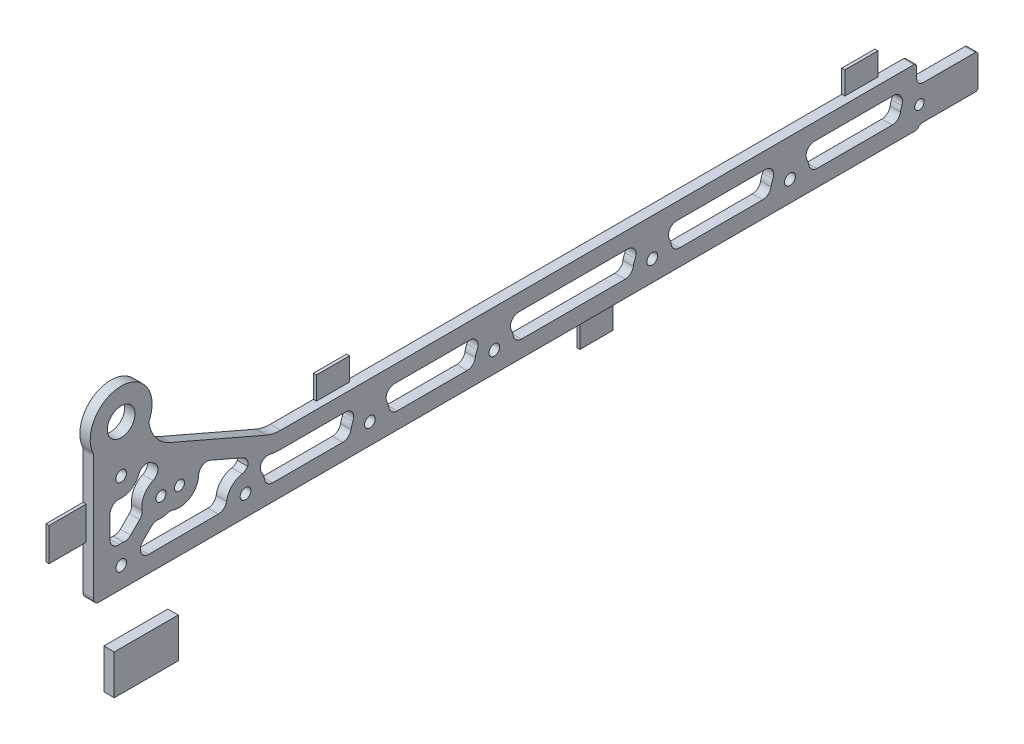
SolidWorks part; units mm, degrees
note: The reader was unsure of these and kept them because the rebuilt part matched: thickness of "Base-Flange1", "Sheet-Metal1", "Sheet-Metal4", "Sheet-Metal5", "Sheet-Metal6", "Sheet-Metal7", "Sheet-Metal9", "Sheet-Metal10", "Sheet-Metal13", "Sheet-Metal14", "Sheet-Metal27", "Sheet-Metal29", "Sheet-Metal31", "Sheet-Metal32", "Sheet-Metal33", "Sheet-Metal34", "Sheet-Metal35", "Sheet-Metal37".
material "6061-T6 (SS)"
ref_plane "Front Plane" through (0, 0, 0) normal (0, 0, 1) x (1, 0, 0)
ref_plane "Top Plane" through (0, 0, 0) normal (0, 1, 0) x (1, 0, 0)
ref_plane "Right Plane" through (0, 0, 0) normal (1, 0, 0) x (0, 0, -1)
sketch "Sketch1" plane through (0, 0, 0) normal (1, 0, 0) x (0, 0, -1)
  line L0 (0, 24.765) -> (57.15, 0)
  line L1 (-25.4, -26.67) -> (-25.4, 24.765)
  line L2 (-25.4, 24.765) -> (0, 24.765) construction
  line L4 (-25.4, -26.67) -> (168.275, -26.67)
  line L5 (0, 24.765) -> (0, -26.67) construction
  line L6 (0, 0) -> (57.15, 0) construction
  line L7 (0, 10.9239) -> (25.2089, 0) construction
  line L8 (57.15, 0) -> (168.275, 0)
  line L9 (168.275, 0) -> (168.275, -26.67)
  line L10 (0, -2.9172) -> (-6.7321, 0) construction
  line L11 (0, 24.765) -> (0, 33.5994)
  line L13 (-25.4, 33.5994) -> (-25.4, 24.765)
  circle A0 centre (-12.7, 40.005) radius 6.35
  arc A1 (-25.4, 33.5994) -> (0, 33.5994) centre (-12.7, 40.005) cw
  point P20 (-12.7, 24.765)
  dimension "D8" = 26.1888
  dimension "D9" = 66.675
  dimension "D10" = 1.524
  dimension "D1" = 26.67
  dimension "D2" = 57.15
  dimension "D3" = 15.24
  dimension "D4" = 25.4
  dimension "D5" = 12.7
  dimension "D6" = 193.675
  dimension "D7" = 25.4
base flange "Base-Flange1" sketch "Sketch1" thickness 4.7625 reverse thickness direction no parameters "D1"=0.7366
sketch "Sketch6" plane through (0, 0, 0) normal (1, 0, 0) x (0, 0, -1)
  line L0 (-12.7, 24.765) -> (-12.7, -17.145) construction
  line L1 (0, 24.765) -> (-25.4, 24.765) construction
  line L2 (114.3, -17.145) -> (-12.7, -17.145) construction
  line L3 (-12.7, -17.145) -> (9.1281, -17.145) construction
  line L4 (0, 10.9239) -> (25.2089, 0) construction
  line L5 (57.15, 0) -> (0, 24.765) construction
  line L6 (0, 24.765) -> (0, -26.67) construction
  line L7 (0, 0) -> (57.15, 0) construction
  line L8 (-25.4, 24.765) -> (0, 24.765) construction
  line L9 (168.275, -26.67) -> (168.275, 0) construction
  line L10 (-25.4, 33.5994) -> (-25.4, -26.67) construction
  line L11 (-25.4, -26.67) -> (168.275, -26.67) construction
  line L14 (0, 10.9239) -> (25.2089, 0) construction
  line L15 (8.2346, 7.3555) -> (16.9743, 3.5683) construction
  circle A0 centre (-12.7, 18.415) radius 1.6383
  circle A6 centre (8.2346, 7.3555) radius 1.6383
  circle A7 centre (-12.7, 8.89) radius 1.6383
  circle A8 centre (-12.7, -0.635) radius 1.6383
  circle A9 centre (-12.7, -10.16) radius 1.6383
  circle A12 centre (16.9743, 3.5683) radius 1.6383
  circle A15 centre (-12.7, -17.145) radius 1.6383
  circle A16 centre (9.1281, -17.145) radius 1.6383
  circle A17 centre (30.9562, -17.145) radius 1.6383
  circle A18 centre (52.7844, -17.145) radius 1.6383
  circle A19 centre (74.6125, -17.145) radius 1.6383
  circle A20 centre (96.4406, -17.145) radius 1.6383
  circle A21 centre (118.2687, -17.145) radius 1.6383
  circle A22 centre (140.0969, -17.145) radius 1.6383
  circle A23 centre (-12.7, -29.21) radius 1.6383 [skipped]
  circle A24 centre (-12.7, -19.685) radius 1.6383 [skipped]
  circle A25 centre (161.925, -17.145) radius 1.6383
  point P38 (12.6045, 5.4619)
  point P68 (161.925, -17.145)
  dimension "D2" = 3.2766
  dimension "D3" = 6.35
  dimension "D5" = 9.525
  dimension "D6" = 9
  dimension "D7" = 6.35
  dimension "D9" = 0.5655
  dimension "D1" = 9.525
  dimension "D8" = 9.525
  dimension "D4" = 6
sketch "Sketch13" plane through (0, 0, 0) normal (1, 0, 0) x (0, 0, -1)
  line L0 (-25.4, -26.67) -> (168.275, -26.67) construction
  line L2 (-25.4, 33.5994) -> (-25.4, -26.67) construction
  line L4 (5.5991, 1.2807) -> (14.1081, 1.2807) construction
  circle A0 centre (5.5991, 1.2807) radius 2.286
  circle A1 centre (14.1081, 1.2807) radius 2.286
  dimension "D1" = 4.572
  dimension "D2" = 13.081
  dimension "D3" = 27.9507
  dimension "D4" = 30.9991
extrude "Cut-Extrude1" cut sketch "Sketch13" against normal through all normal cut yes
hole_wizard "CSK for #10 Flat Head Machine Screw (100)2" [suppressed] positions "Sketch9" profile "Sketch10" countersink size "#10" standard "ANSI Inch"
sketch "Sketch9" plane through (-1.524, 0, 0) normal (-1, 0, 0) x (0, 0, 1)
  point P60 (12.7, 27.5433)
  point P63 (12.7, 18.0183)
  point P66 (12.7, 8.4933)
  point P69 (12.7, -1.0317)
  point P72 (12.7, -10.5567)
  point P75 (12.7, -20.0817)
  point P78 (-8.3159, 11.8745)
  point P81 (-15.9573, 6.1882)
  point P84 (-6.35, -12.7)
  point P87 (-15.4214, -12.7)
  point P90 (-24.4929, -12.7)
  point P93 (-33.5643, -12.7)
  point P96 (-42.6357, -12.7)
  point P99 (-51.7071, -12.7)
  point P102 (-60.7786, -12.7)
  point P105 (-69.85, -12.7)
sketch "Sketch10" plane through (-1.524, 27.5433, 12.7) normal (0, 1, 0) x (0, 0, 1)
  line L0 (0, 0) -> (0, 1.524)
  line L1 (0, 1.524) -> (1.6383, 1.524)
  line L2 (1.6383, 1.524) -> (1.6383, 1.3208)
  line L3 (1.6383, 1.3208) -> (2.9591, 0)
  line L5 (2.9591, 0) -> (0, 0)
  line L6 (-1.6383, 1.3208) -> (-2.9591, 0) construction
  line L11 (0, -6.35) -> (0, 107.95) construction
  dimension "Thru Hole Dia." = 3.2766
  dimension "Thru Hole Depth" = 1.524
  dimension "Near C'Sink Dia." = 5.9182
  dimension "Near C'Sink Angle" = 90
hole_wizard "CSK for #10 Flat Head Machine Screw (100)3" [suppressed] positions "Sketch11" profile "Sketch12" countersink size "#10" standard "ANSI Inch"
sketch "Sketch11" plane through (0, 0, 0) normal (1, 0, 0) x (0, 0, -1)
  point P108 (-12.7, 27.5433)
  point P111 (-12.7, 18.0183)
  point P114 (-12.7, 8.4933)
  point P117 (-12.7, -1.0317)
  point P120 (-12.7, -10.5567)
  point P123 (-12.7, -20.0817)
  point P126 (8.3159, 11.8745)
  point P129 (15.9573, 6.1882)
  point P132 (6.35, -12.7)
  point P135 (15.4214, -12.7)
  point P138 (24.4929, -12.7)
  point P141 (33.5643, -12.7)
  point P144 (42.6357, -12.7)
  point P147 (51.7071, -12.7)
  point P150 (60.7786, -12.7)
  point P153 (69.85, -12.7)
sketch "Sketch12" plane through (0, 27.5433, 12.7) normal (0, 1, 0) x (0, 0, -1)
  line L0 (0, 0) -> (0, 2.286)
  line L1 (0, 2.286) -> (1.6383, 2.286)
  line L2 (1.6383, 2.286) -> (1.6383, 1.3208)
  line L3 (1.6383, 1.3208) -> (2.9591, 0)
  line L5 (2.9591, 0) -> (0, 0)
  line L6 (-1.6383, 1.3208) -> (-2.9591, 0) construction
  line L11 (0, -6.35) -> (0, 107.95) construction
  dimension "Thru Hole Dia." = 3.2766
  dimension "Thru Hole Depth" = 2.286
  dimension "Near C'Sink Dia." = 5.9182
  dimension "Near C'Sink Angle" = 90
fillet "Fillet1" radius 16.51 2 edges at (-2.3813, 0, -57.15) (-2.3813, 24.765, 0)
hole_wizard "#10 (0.1935) Diameter Hole1" positions "Sketch14" profile "Sketch15" hole size "#10" standard "ANSI Inch" end condition through all
sketch "Sketch14" plane through (0, 0, 0) normal (1, 0, 0) x (0, 0, -1)
  line L1 (158.75, -17.145) -> (101.6, -17.145) construction
  line L2 (101.6, -17.145) -> (44.45, -17.145) construction
  line L3 (44.45, -17.145) -> (-12.7, -17.145) construction
  line L4 (-12.7, -17.145) -> (-12.7, 18.415) construction
  line L5 (-12.7, 18.415) -> (-12.7, 40.005) construction
  line L7 (-25.4, -26.67) -> (168.275, -26.67) construction
  point P41 (-12.7, -17.145)
  point P44 (44.45, -17.145)
  point P47 (101.6, -17.145)
  point P50 (158.75, -17.145)
  point P58 (-12.7, 18.415)
  dimension "D1" = 21.59
  dimension "D2" = 9.525
  dimension "D3" = 57.15
sketch "Sketch15" plane through (0, -17.145, 12.7) normal (0, 1, 0) x (0, 0, -1)
  line L0 (0, 0) -> (0, 4.7625)
  line L1 (0, 4.7625) -> (2.4574, 4.7625)
  line L2 (2.4574, 4.7625) -> (2.4574, 0)
  line L5 (2.4574, 0) -> (0, 0)
  line L11 (0, -6.35) -> (0, 107.95) construction
  dimension "Thru Hole Dia." = 4.9149
  dimension "Thru Hole Depth" = 4.7625
sketch "Sketch22" [suppressed] plane through (0, 0, 0) normal (1, 0, 0) x (0, 0, -1)
  line L1 (-75.7892, -29.5873) -> (-96.2835, -29.5873)
  line L2 (-75.7892, -29.5873) -> (-75.7892, -6.7214)
  line L3 (-75.7892, -6.7214) -> (-96.2835, -6.7214)
  line L4 (-96.2835, -29.5873) -> (-96.2835, -6.7214)
  dimension "D1" = 22.8659
  dimension "D2" = 20.4944
extrude "Boss-Extrude2" [suppressed] add sketch "Sketch22" against normal up to surface (4.7625 mm away) separate body
sketch "Sketch23" [suppressed] plane through (-4.7625, 0, 0) normal (-1, 0, 0) x (0, 0, 1)
  line L0 (25.4, 10.3433) -> (25.4, -4.8967)
  line L1 (25.4, 10.3433) -> (37.5677, 10.3433)
  line L2 (25.4, -4.8967) -> (37.5677, -4.8967)
  line L3 (37.5677, 10.3433) -> (37.5677, -4.8967)
  line L4 (25.4, 34.8694) -> (25.4, -25.4) construction
  line L5 (-91.8385, 0) -> (-76.5985, 0)
  line L6 (-91.8385, 0) -> (-91.8385, 9.2269)
  line L7 (-76.5985, 0) -> (-76.5985, 9.2269)
  line L8 (-91.8385, 9.2269) -> (-76.5985, 9.2269)
  line L9 (-114.3, 0) -> (-60.7335, 0) construction
  line L10 (-26.0856, -25.4) -> (-41.3256, -25.4)
  line L11 (-26.0856, -25.4) -> (-26.0856, -39.6506)
  line L12 (-41.3256, -25.4) -> (-41.3256, -39.6506)
  line L13 (-26.0856, -39.6506) -> (-41.3256, -39.6506)
  line L14 (25.4, -25.4) -> (-114.3, -25.4) construction
  dimension "D1" = 15.24
  dimension "D2" = 19.0897
  dimension "D3" = 14.2506
extrude "Boss-Extrude3" [suppressed] add sketch "Sketch23" against normal blind 1.27
fillet "Fillet4" radius 2.54 5 edges at (-2.3813, -26.67, -168.275) (-2.3813, 0, -168.275) (-2.3813, 33.5994, 0) (-2.3813, 33.5994, 25.4) (-2.3813, -26.67, 25.4)
hole_wizard "#10-32 Tapped Hole1" [suppressed] positions "Sketch18" profile "Sketch19" tap size "#10-32" standard "ANSI Inch"
sketch "Sketch18" plane through (0, 0, 0) normal (1, 0, 0) x (0, 0, -1)
  line L0 (137.16, 0) -> (60.7335, 0) construction
  line L1 (139.7, -22.86) -> (139.7, -2.54) construction
  point P1 (86.36, -6.35)
  dimension "D1" = 6.35
  dimension "D2" = 53.34
sketch "Sketch19" plane through (0, -6.35, -86.36) normal (0, 1, 0) x (0, 0, -1)
  line L0 (0, 0) -> (0, 13.2529)
  line L1 (0, 13.2529) -> (2.0193, 12.0396)
  line L2 (2.0193, 12.0396) -> (2.0193, 0)
  line L5 (2.0193, 0) -> (0, 0)
  line L10 (0, 13.2529) -> (-2.0193, 12.0396) construction
  line L11 (0, -6.35) -> (0, 107.95) construction
  dimension "Tap Drill Dia." = 4.0386
  dimension "Tap Drill Depth" = 12.0396
  dimension "Drill Angle" = 118
cosmetic thread "Hole Thread1" [suppressed]
pattern_linear "LPattern1" [suppressed] count 3 spacing 19.05
sketch "Sketch24" plane through (0, 0, 0) normal (1, 0, 0) x (0, 0, -1)
  line L0 (-12.7, -17.145) -> (5.5991, 1.2807) construction
  line L1 (-9.9967, -19.8298) -> (8.3024, -1.4041)
  line L2 (-15.4033, -14.4602) -> (2.8957, 3.9655)
  line L10 (-17.78, 33.0212) -> (-17.78, -19.05)
  line L11 (-17.78, -19.05) -> (160.655, -19.05)
  line L12 (160.655, -19.05) -> (160.655, -7.62)
  line L13 (160.655, -7.62) -> (60.5734, -7.62)
  line L14 (50.9791, -5.6306) -> (6.7866, 13.5195)
  line L15 (-17.78, 33.0212) -> (-17.78, -19.05)
  line L16 (-17.78, -19.05) -> (160.655, -19.05)
  line L17 (160.655, -19.05) -> (160.655, -7.62)
  line L18 (160.655, -7.62) -> (60.5734, -7.62)
  line L19 (50.9791, -5.6306) -> (6.7866, 13.5195)
  circle A0 centre (-12.7, 18.415) radius 8.8074
  circle A1 centre (-12.7, -17.145) radius 8.8074
  circle A2 centre (44.45, -17.145) radius 8.8074
  circle A3 centre (101.6, -17.145) radius 8.8074
  circle A4 centre (158.75, -17.145) radius 8.8074
  circle A5 centre (5.5991, 1.2807) radius 8.8074
  circle A6 centre (14.1081, 1.2807) radius 8.8074
  arc A7 (52.1248, -12.8244) -> (56.1442, -7.21) centre (55.4449, -10.9553) cw
  arc A8 (41.6198, -8.8047) -> (41.9104, -1.7008) centre (40.3955, -5.1967) ccw
  arc A9 (-4.5133, 15.167) -> (1.3944, 16.7481) centre (-0.9718, 13.762) cw
  arc A10 (1.9484, 9.2959) -> (2.5526, 15.8855) centre (0.3691, 12.7632) ccw
  arc A11 (-2.7721, -12.5552) -> (-0.0687, -19.05) centre (-0.0687, -15.24) ccw
  circle A15 centre (-12.7, 18.415) radius 2.4574 construction
  arc A23 (-7.3762, 31.4345) -> (6.7866, 13.5195) centre (16.3809, 35.6601) ccw
  arc A24 (-6.6622, 37.3296) -> (-18.7036, 37.2538) centre (-12.7, 40.005) ccw
  arc A25 (-6.6622, 37.3296) -> (-7.3762, 31.4345) centre (2.6268, 33.2137) ccw
  arc A26 (-6.6622, 37.3296) -> (-7.3762, 31.4345) centre (2.6268, 33.2137) ccw
  arc A27 (-17.78, 33.0212) -> (-18.7036, 37.2538) centre (-27.94, 33.0212) ccw
  arc A28 (50.9791, -5.6306) -> (60.5734, -7.62) centre (60.5734, 16.51) ccw
  arc A29 (-7.7491, 35.6345) -> (6.7866, 13.5195) centre (16.3809, 35.6601) ccw
  arc A30 (-7.7491, 35.6345) -> (-18.7036, 37.2538) centre (-12.7, 40.005) ccw
  arc A34 (50.9791, -5.6306) -> (60.5734, -7.62) centre (60.5734, 16.51) ccw
  arc A35 (-17.78, 33.0212) -> (-18.7036, 37.2538) centre (-27.94, 33.0212) ccw
  dimension "D2" = 6.35
  dimension "D3" = 3.81
  dimension "D1" = 7.62
  dimension "D4" = 3.81
  dimension "D5" = 3.81
extrude "Cut-Extrude2" [suppressed] cut sketch "Sketch24" against normal through all contours A29 A9 A0 L15 A1 L2 A5 A10 | A2 A8 L19 A6 A5 L1 A1 L16 | A34 A7 A2 L16 A3 L18 | A4 L18 A3 L16
fillet "Fillet5" [suppressed] radius 3.81
sketch "Sketch25" [suppressed] plane through (-4.7625, 0, 0) normal (-1, 0, 0) x (0, 0, 1)
  line L0 (22.86, -25.4) -> (-165.735, -25.4) construction
  line L1 (25.4, 34.2912) -> (25.4, -22.86) construction
  line L4 (-89.7914, -7.62) -> (-60.7335, -7.62) construction
  circle A0 centre (-63.5, -17.145) radius 4.7625
  dimension "D1" = 9.525
  dimension "D4" = 4.7625
  dimension "D2" = 8.255
  dimension "D3" = 88.9
extrude "Boss-Extrude4" [suppressed] add sketch "Sketch25" against normal up to surface (4.7625 mm away)
sketch "Sketch26" [suppressed] plane through (-4.7625, 0, 0) normal (-1, 0, 0) x (0, 0, 1)
  circle A0 centre (-63.5, -17.145) radius 2.3813
  dimension "D1" = 4.7625
fillet "Fillet6" [suppressed] radius 6.35
hole_wizard " Tapped Hole2" [suppressed] positions "Sketch29" profile "Sketch30" tap size "#8-32" standard "ANSI Inch"
sketch "Sketch29" [suppressed] plane through (-4.7625, 0, 0) normal (-1, 0, 0) x (0, 0, 1)
  point P0 (-63.5, -17.145)
sketch "Sketch30" plane through (-4.7625, -17.145, -63.5) normal (0, 1, 0) x (0, 0, 1)
  line L0 (0, 0) -> (0, 4.7625)
  line L1 (0, 4.7625) -> (2.0193, 4.7625)
  line L2 (2.0193, 4.7625) -> (2.0193, 0)
  line L5 (2.0193, 0) -> (0, 0)
  line L11 (0, -6.35) -> (0, 107.95) construction
  dimension "Thru Tap Drill Dia." = 3.4544
  dimension "Thru Tap Drill Depth" = 4.7625
cosmetic thread "Hole Thread2" [suppressed]
fillet "Fillet7" [suppressed] radius 3.048
sketch "Sketch32" [suppressed] plane through (-4.7625, 0, 0) normal (-1, 0, 0) x (0, 0, 1)
  line L0 (-184.253, -26.3369) -> (-208.5192, -26.3369)
  line L1 (-184.253, -26.3369) -> (-184.253, -4.36)
  line L2 (-208.5192, -26.3369) -> (-208.5192, -4.36)
  line L3 (-184.253, -4.36) -> (-208.5192, -4.36)
  dimension "D1" = 41.2067
  dimension "D2" = 32.5075
extrude "Boss-Extrude5" [suppressed] add sketch "Sketch32" against normal up to surface (4.7625 mm away) separate body
sketch "Sketch33" [suppressed] plane through (0, 0, 0) normal (1, 0, 0) x (0, 0, -1)
  line L0 (-25.4, 34.2912) -> (-25.4, -22.86) construction
  line L2 (-25.4, -10.134) -> (-25.4, 5.106)
  line L3 (-25.4, -10.134) -> (-34.1173, -10.134)
  line L4 (-25.4, 5.106) -> (-34.1173, 5.106)
  line L5 (-34.1173, -10.134) -> (-34.1173, 5.106)
  line L6 (168.275, -6.1621) -> (168.275, -21.4021)
  line L7 (168.275, -6.1621) -> (174.9331, -6.1621)
  line L8 (168.275, -21.4021) -> (174.9331, -21.4021)
  line L9 (174.9331, -6.1621) -> (174.9331, -21.4021)
  line L10 (168.275, -22.86) -> (168.275, -2.54) construction
  line L11 (62.6695, -25.4) -> (77.9095, -25.4)
  line L12 (62.6695, -25.4) -> (62.6695, -34.9885)
  line L13 (77.9095, -25.4) -> (77.9095, -34.9885)
  line L14 (62.6695, -34.9885) -> (77.9095, -34.9885)
  line L15 (-22.86, -25.4) -> (165.735, -25.4) construction
  line L16 (122.9051, 0) -> (138.1451, 0)
  line L17 (122.9051, 0) -> (122.9051, 11.3683)
  line L18 (138.1451, 0) -> (138.1451, 11.3683)
  line L19 (122.9051, 11.3683) -> (138.1451, 11.3683)
  line L20 (165.735, 0) -> (60.7335, 0) construction
  line L21 (20.9085, 16.51) -> (34.7772, 10.192)
  line L22 (20.9085, 16.51) -> (24.2006, 23.7364)
  line L23 (34.7772, 10.192) -> (38.0693, 17.4184)
  line L24 (24.2006, 23.7364) -> (38.0693, 17.4184)
  line L25 (53.889, 1.4856) -> (9.5634, 21.6783) construction
  dimension "D1" = 15.24
  dimension "D2" = 7.9409
extrude "Boss-Extrude6" [suppressed] add sketch "Sketch33" against normal blind 1.27
sketch "Sketch35" [suppressed] plane through (0, 0, 0) normal (1, 0, 0) x (0, 0, -1)
  line L0 (-25.4, -3.4789) -> (-25.4, 11.7611)
  line L1 (-25.4, -3.4789) -> (-43.416, -3.4789)
  line L2 (-25.4, 11.7611) -> (-43.416, 11.7611)
  line L3 (-43.416, -3.4789) -> (-43.416, 11.7611)
  line L4 (-25.4, 34.2912) -> (-25.4, -22.86) construction
  line L5 (15.126, 19.1443) -> (28.9947, 12.8263)
  line L6 (15.126, 19.1443) -> (19.3832, 28.4895)
  line L7 (28.9947, 12.8263) -> (33.2519, 22.1715)
  line L8 (19.3832, 28.4895) -> (33.2519, 22.1715)
  line L9 (53.889, 1.4856) -> (9.5634, 21.6783) construction
  line L10 (83.6261, -25.4) -> (98.8661, -25.4)
  line L11 (83.6261, -25.4) -> (83.6261, -34.1917)
  line L12 (98.8661, -25.4) -> (98.8661, -34.1917)
  line L13 (83.6261, -34.1917) -> (98.8661, -34.1917)
  line L14 (-22.86, -25.4) -> (165.735, -25.4) construction
  line L15 (126.1294, 0) -> (141.3694, 0)
  line L16 (126.1294, 0) -> (126.1294, 8.0687)
  line L17 (141.3694, 0) -> (141.3694, 8.0687)
  line L18 (126.1294, 8.0687) -> (141.3694, 8.0687)
  line L19 (165.735, 0) -> (60.7335, 0) construction
  line L20 (168.275, -21.2983) -> (168.275, -6.0583)
  line L21 (168.275, -21.2983) -> (173.5241, -21.2983)
  line L22 (168.275, -6.0583) -> (173.5241, -6.0583)
  line L23 (173.5241, -21.2983) -> (173.5241, -6.0583)
  line L24 (168.275, -22.86) -> (168.275, -2.54) construction
  dimension "D1" = 15.24
  dimension "D2" = 5.2491
extrude "Boss-Extrude7" [suppressed] add sketch "Sketch35" against normal blind 1.27
sketch "Sketch37" plane through (-4.7625, 0, 0) normal (-1, 0, 0) x (0, 0, 1)
  line L0 (-165.735, -26.67) -> (-353.0505, -26.67)
  line L2 (-355.6, -25.019) -> (-381, -25.019)
  line L3 (-381, -25.019) -> (-381, -9.271)
  line L4 (-381, -9.271) -> (-355.6, -9.271)
  line L5 (-352.806, -6.477) -> (-352.806, 0)
  line L6 (-352.806, 0) -> (-165.735, 0)
  line L7 (-168.275, -24.13) -> (-168.275, -2.54) construction
  line L8 (-168.275, -24.13) -> (-168.275, -2.54)
  line L9 (-381, -17.145) -> (-323.8598, -17.145) construction
  line L11 (-355.6, -25.019) -> (-355.6, -4.0005) construction
  line L12 (25.4, 33.0212) -> (25.4, -24.13) construction
  arc A0 (-165.735, 0) -> (-168.275, -2.54) centre (-165.735, -2.54) ccw construction
  arc A1 (-168.275, -24.13) -> (-165.735, -26.67) centre (-165.735, -24.13) ccw construction
  arc A2 (-165.735, 0) -> (-168.275, -2.54) centre (-165.735, -2.54) ccw
  arc A3 (-168.275, -24.13) -> (-165.735, -26.67) centre (-165.735, -24.13) ccw
  arc A4 (-353.0505, -26.67) -> (-355.6, -25.019) centre (-355.6, -27.813) ccw
  arc A5 (-355.6, -9.271) -> (-352.806, -6.477) centre (-355.6, -6.477) ccw
  circle A6 centre (-231.3432, -17.145) radius 2.4892
  circle A7 centre (-294.5892, -17.145) radius 2.4892
  circle A9 centre (-354.076, -17.145) radius 2.159
  dimension "D4" = 2.794
  dimension "D5" = 25.4
  dimension "D6" = 254.254
  dimension "D7" = 317.5
  dimension "D8" = 4.9784
  dimension "D9" = 4.318
  dimension "D1" = 1.651
  dimension "D2" = 9.525
  dimension "D3" = 381
  dimension "D10" = 379.476
extrude "Boss-Extrude8" add sketch "Sketch37" against normal through all
sketch "Sketch39" [suppressed] plane through (-4.7625, 0, 0) normal (-1, 0, 0) x (0, 0, 1)
  line L0 (-146.9414, -7.62) -> (-351.0058, -7.62)
  line L1 (-146.2772, -17.78) -> (-345.477, -17.78)
  circle A0 centre (-354.076, -15.875) radius 8.8075
  circle A1 centre (-294.5892, -15.875) radius 8.8075
  circle A2 centre (-231.3432, -15.875) radius 8.8074
  circle A3 centre (-158.75, -15.875) radius 8.8074
  arc A4 (-150.0435, -14.5452) -> (-150.5072, -12.7722) centre (-158.75, -15.875) ccw construction
  dimension "D1" = 1.386
extrude "Cut-Extrude3" [suppressed] cut sketch "Sketch39" against normal through all contours A1 L0 A0 L1 | A2 L0 A1 L1 | A3 L0 A2 L1
fillet "Fillet8" [suppressed] radius 3.81
sketch "Sketch46" plane through (0, 0, 0) normal (1, 0, 0) x (0, 0, -1)
  line L0 (-12.7, -17.145) -> (5.5991, 1.2807) construction
  line L1 (-9.9967, -19.8298) -> (8.3024, -1.4041)
  line L2 (-15.4033, -14.4602) -> (2.8957, 3.9655)
  line L3 (44.45, -17.145) -> (51.3619, -1.1944) construction
  line L4 (101.6, -17.145) -> (101.6, 0) construction
  line L5 (352.806, 0) -> (60.5734, 0) construction
  line L6 (158.75, -17.145) -> (158.75, 0) construction
  line L7 (231.3432, -17.145) -> (231.3432, 3.1296) construction
  line L8 (294.5892, -17.145) -> (294.5892, 6.8724) construction
  line L9 (297.7642, -17.145) -> (297.7642, 6.8724)
  line L10 (234.5182, -17.145) -> (234.5182, 3.1296)
  line L11 (161.925, -17.145) -> (161.925, 0)
  line L12 (104.775, -17.145) -> (104.775, 0)
  line L13 (46.4846, -20.4351) -> (54.4474, -2.0594)
  line L14 (291.4142, -17.145) -> (291.4142, 6.8724)
  line L15 (228.1682, -17.145) -> (228.1682, 3.1296)
  line L16 (-17.78, -19.05) -> (349.9732, -19.05)
  line L17 (355.6, -17.399) -> (373.38, -17.399)
  line L18 (373.38, -17.399) -> (373.38, -16.891)
  line L19 (373.38, -16.891) -> (355.6, -16.891)
  line L21 (345.2489, -7.62) -> (60.5734, -7.62)
  line L22 (50.9791, -5.6306) -> (6.7866, 13.5195)
  line L23 (-17.78, 33.0212) -> (-17.78, -19.05)
  line L24 (-17.78, -19.05) -> (349.9732, -19.05)
  line L25 (355.6, -17.399) -> (373.38, -17.399)
  line L26 (373.38, -17.399) -> (373.38, -16.891)
  line L27 (373.38, -16.891) -> (355.6, -16.891)
  line L29 (345.2489, -7.62) -> (60.5734, -7.62)
  line L30 (50.9791, -5.6306) -> (6.7866, 13.5195)
  line L31 (-17.78, 33.0212) -> (-17.78, -19.05)
  line L32 (155.575, -17.145) -> (155.575, 0)
  line L33 (98.425, -17.145) -> (98.425, 0)
  line L34 (40.5621, -18.1318) -> (49.326, 2.0925)
  line L35 (44.45, -17.145) -> (50.5452, -3.0793) construction
  line L36 (47.3632, -18.4074) -> (53.4584, -4.3417) construction
  line L37 (41.5368, -15.8826) -> (47.6319, -1.8169) construction
  arc A0 (1.9484, 9.2959) -> (2.5526, 15.8855) centre (0.3691, 12.7632) ccw
  arc A1 (22.9072, 0.8978) -> (28.2285, 4.228) centre (26.7136, 0.7321) cw
  arc A2 (93.7478, -13.1557) -> (90.3511, -7.62) centre (90.3511, -11.43) ccw
  arc A3 (-2.7721, -12.5552) -> (-0.0687, -19.05) centre (-0.0687, -15.24) ccw
  arc A4 (109.4522, -13.1557) -> (112.8489, -7.62) centre (112.8489, -11.43) cw
  arc A5 (150.8978, -13.1557) -> (147.5011, -7.62) centre (147.5011, -11.43) ccw
  arc A6 (166.6022, -13.1557) -> (169.9989, -7.62) centre (169.9989, -11.43) cw
  arc A7 (223.491, -13.1557) -> (220.0943, -7.62) centre (220.0943, -11.43) ccw
  circle A8 centre (-12.7, 18.415) radius 8.8074
  circle A9 centre (5.5991, 1.2807) radius 8.8074
  circle A10 centre (14.1081, 1.2807) radius 8.8074
  circle A11 centre (-12.7, -17.145) radius 8.8074
  circle A12 centre (44.45, -17.145) radius 8.8074
  circle A13 centre (101.6, -17.145) radius 8.8074
  arc A14 (239.1954, -13.1557) -> (242.5921, -7.62) centre (242.5921, -11.43) cw
  circle A15 centre (158.75, -17.145) radius 8.8074
  arc A16 (355.6, -17.399) -> (349.9732, -19.05) centre (355.6, -27.813) ccw
  arc A17 (345.2489, -7.62) -> (355.6, -16.891) centre (355.6, -6.477) ccw
  arc A18 (50.9791, -5.6306) -> (60.5734, -7.62) centre (60.5734, 16.51) ccw
  arc A19 (-7.3762, 31.4345) -> (6.7866, 13.5195) centre (16.3809, 35.6601) ccw
  arc A20 (-6.6622, 37.3296) -> (-7.3762, 31.4345) centre (2.6268, 33.2137) ccw
  arc A21 (-6.6622, 37.3296) -> (-18.7036, 37.2538) centre (-12.7, 40.005) ccw
  arc A22 (-17.78, 33.0212) -> (-18.7036, 37.2538) centre (-27.94, 33.0212) ccw
  arc A23 (355.6, -17.399) -> (349.9732, -19.05) centre (355.6, -27.813) ccw
  arc A24 (345.2489, -7.62) -> (355.6, -16.891) centre (355.6, -6.477) ccw
  arc A25 (50.9791, -5.6306) -> (60.5734, -7.62) centre (60.5734, 16.51) ccw
  arc A26 (-7.3762, 31.4345) -> (6.7866, 13.5195) centre (16.3809, 35.6601) ccw
  arc A27 (-6.6622, 37.3296) -> (-7.3762, 31.4345) centre (2.6268, 33.2137) ccw
  arc A28 (-6.6622, 37.3296) -> (-18.7036, 37.2538) centre (-12.7, 40.005) ccw
  arc A29 (-17.78, 33.0212) -> (-18.7036, 37.2538) centre (-27.94, 33.0212) ccw
  circle A30 centre (231.3432, -17.145) radius 8.8074
  circle A31 centre (294.5892, -17.145) radius 8.8075
  circle A32 centre (354.076, -17.145) radius 8.8075
  circle A33 centre (-12.7, -17.145) radius 2.4574 construction
  arc A34 (-4.5133, 15.167) -> (1.3944, 16.7481) centre (-0.9718, 13.762) cw
  arc A35 (286.737, -13.1557) -> (283.3403, -7.62) centre (283.3403, -11.43) ccw
  arc A36 (302.4414, -13.1557) -> (305.8381, -7.62) centre (305.8381, -11.43) cw
  dimension "D2" = 6.35
  dimension "D3" = 3.81
  dimension "D4" = 3.81
  dimension "D6" = 3.175
  dimension "D8" = 2.8676
  dimension "D1" = 7.62
  dimension "D5" = 3.81
  dimension "D7" = 3.175
extrude "Cut-Extrude4" cut sketch "Sketch46" against normal through all
fillet "Fillet10" radius 3.81 23 edges at (-2.3813, -12.1165, -346.8451) (-2.3813, -19.05, -345.477) (-2.3813, -19.05, -303.1882) (-2.3813, -19.05, -285.9902) (-2.3813, -19.05, -239.9422) (-2.3813, -19.05, -222.7442) (-2.3813, -19.05, -167.349) (-2.3813, -19.05, -150.151) (-2.3813, -19.05, -110.199) (-2.3813, -19.05, -93.001) (-2.3813, -19.05, -53.049) (-2.3813, -19.05, -35.851) (-2.3813, -10.8694, -50.6297) (-2.3813, -6.2722, -52.6218) (-2.3813, -7.0383, -2.7069) (-2.3813, -6.431, -9.8536) (-2.3813, -3.8065, -46.7697) (-2.3813, -8.3446, -44.8032) (-2.3813, -1.6688, 2.6998) (-2.3813, -9.9502, 17.78) (-2.3813, 11.2202, 17.78) (-2.3813, -8.826, 9.8078) (-2.3813, -7.62, -345.2489)
fillet "Fillet9" radius 1.27 4 edges at (-2.3812, -26.67, -353.0505) (-2.3812, -25.019, -381) (-2.3812, -9.271, -381) (-2.3812, 0, -352.806)
sketch "Sketch41" plane through (-4.7625, 0, 0) normal (-1, 0, 0) x (0, 0, 1)
  line L0 (-351.536, 0) -> (-60.5734, 0) construction
  line L1 (-338.3853, 0) -> (-323.1453, 0)
  line L2 (-338.3853, 0) -> (-338.3853, 10.4268)
  line L3 (-338.3853, 10.4268) -> (-323.1453, 10.4268)
  line L4 (-323.1453, 0) -> (-323.1453, 10.4268)
  line L5 (22.86, -26.67) -> (-352.3299, -26.67) construction
  line L6 (-216.7038, -26.67) -> (-201.4638, -26.67)
  line L7 (-216.7038, -26.67) -> (-216.7038, -39.9756)
  line L8 (-216.7038, -39.9756) -> (-201.4638, -39.9756)
  line L9 (-201.4638, -26.67) -> (-201.4638, -39.9756)
  line L10 (25.4, 33.0212) -> (25.4, -24.13) construction
  line L11 (-95.6188, 0) -> (-80.3788, 0)
  line L12 (-95.6188, 0) -> (-95.6188, 10.4268)
  line L13 (-95.6188, 10.4268) -> (-80.3788, 10.4268)
  line L14 (-80.3788, 0) -> (-80.3788, 10.4268)
  line L15 (25.4, 11.9478) -> (42.4659, 11.9478)
  line L16 (25.4, 11.9478) -> (25.4, -3.2922)
  line L17 (25.4, -3.2922) -> (42.4659, -3.2922)
  line L18 (42.4659, 11.9478) -> (42.4659, -3.2922)
  dimension "D1" = 15.24
  dimension "D2" = 17.0659
extrude "Boss-Extrude9" add sketch "Sketch41" against normal blind 1.397
sketch "Sketch43" plane through (0, 0, 0) normal (1, 0, 0) x (0, 0, -1)
  line L1 (-15.8749, -49.9791) -> (13.5373, -49.9791)
  line L2 (-15.8749, -49.9791) -> (-15.8749, -68.2456)
  line L3 (-15.8749, -68.2456) -> (13.5373, -68.2456)
  line L4 (13.5373, -49.9791) -> (13.5373, -68.2456)
  dimension "D1" = 18.2665
  dimension "D2" = 29.4122
extrude "Boss-Extrude10" add sketch "Sketch43" against normal through all separate body
sketch "Bend-Lines1" [suppressed] plane through (0, 0, 0) normal (0, 1, 0) x (1, 0, 0)
sketch "Bounding-Box1" [suppressed] plane through (0, 0, 0) normal (0, 1, 0) x (1, 0, 0)
sheet metal parameters "Sheet-Metal1" thickness 4.7625 parameters "D1"=0.7366
flat pattern "Flat-Pattern1" [suppressed]
sketch "Bend-Lines2" plane through (0, 0, 0) normal (0, 1, 0) x (1, 0, 0)
sketch3d "Bounding-Box2" [suppressed]
  line L0 (76.2, -25.4, 0) -> (-25.4, -25.4, 0) construction
  line L1 (76.2, 33.8933, 0) -> (-25.4, 33.8933, 0) construction
  line L2 (76.2, -25.4, 0) -> (76.2, 33.8933, 0) construction
  line L3 (-25.4, -25.4, 0) -> (-25.4, 33.8933, 0) construction
sheet metal parameters "Sheet-Metal4" [suppressed] thickness 4.7625 parameters "D1"=0.7366, "D7"=1.524
flat pattern "Flat-Pattern1"
sketch "Bend-Lines2" plane through (0, 0, 0) normal (0, 1, 0) x (1, 0, 0)
sketch3d "Bounding-Box2" [suppressed]
  line L0 (76.2, -25.4, 0) -> (-25.4, -25.4, 0) construction
  line L1 (76.2, 33.8933, 0) -> (-25.4, 33.8933, 0) construction
  line L2 (76.2, -25.4, 0) -> (76.2, 33.8933, 0) construction
  line L3 (-25.4, -25.4, 0) -> (-25.4, 33.8933, 0) construction
sheet metal parameters "Sheet-Metal5" [suppressed] thickness 4.7625 parameters "D1"=0.7366, "D7"=1.524
flat pattern "Flat-Pattern1"
sketch "Bend-Lines2" plane through (0, 0, 0) normal (0, 1, 0) x (1, 0, 0)
sketch3d "Bounding-Box2" [suppressed]
  line L0 (76.2, -25.4, 0) -> (-25.4, -25.4, 0) construction
  line L1 (76.2, 33.8933, 0) -> (-25.4, 33.8933, 0) construction
  line L2 (76.2, -25.4, 0) -> (76.2, 33.8933, 0) construction
  line L3 (-25.4, -25.4, 0) -> (-25.4, 33.8933, 0) construction
sheet metal parameters "Sheet-Metal6" thickness 4.7625 parameters "D1"=0.7366, "D7"=2.286
flat pattern "Flat-Pattern1"
sketch "Bend-Lines2" plane through (0, 0, 0) normal (0, 1, 0) x (1, 0, 0)
sketch3d "Bounding-Box2" [suppressed]
  line L0 (88.8958, 12.7065, 0) -> (-12.7009, 12.699, 0) construction
  line L1 (88.9019, -69.9128, 0) -> (-12.6948, -69.9203, 0) construction
  line L2 (88.8958, 12.7065, 0) -> (88.9019, -69.9128, 0) construction
  line L3 (-12.7009, 12.699, 0) -> (-12.6948, -69.9203, 0) construction
sheet metal parameters "Sheet-Metal7" thickness 4.7625 parameters "D1"=0.7366, "D7"=2.286
flat pattern "Flat-Pattern1"
sketch "Bend-Lines2" plane through (0, 0, 0) normal (0, 1, 0) x (1, 0, 0)
sketch3d "Bounding-Box2" [suppressed]
  line L0 (180.975, 14.224, 0) -> (-14.224, 14.224, 0) construction
  line L1 (180.975, -66.675, 0) -> (-14.224, -66.675, 0) construction
  line L2 (180.975, 14.224, 0) -> (180.975, -66.675, 0) construction
  line L3 (-14.224, 14.224, 0) -> (-14.224, -66.675, 0) construction
sheet metal parameters "Sheet-Metal9" thickness 4.7625 parameters "D1"=0.7366, "D7"=2.286
flat pattern "Flat-Pattern1"
sketch "Bend-Lines2" plane through (0, 0, 0) normal (0, 1, 0) x (1, 0, 0)
sketch3d "Bounding-Box2" [suppressed]
  line L0 (133.35, 14.224, 0) -> (-14.224, 14.224, 0) construction
  line L1 (133.35, -66.675, 0) -> (-14.224, -66.675, 0) construction
  line L2 (133.35, 14.224, 0) -> (133.35, -66.675, 0) construction
  line L3 (-14.224, 14.224, 0) -> (-14.224, -66.675, 0) construction
sheet metal parameters "Sheet-Metal10" thickness 4.7625 parameters "D1"=0.7366, "D7"=2.286
flat pattern "Flat-Pattern1"
sketch "Bend-Lines2" plane through (0, 0, 0) normal (0, 1, 0) x (1, 0, 0)
sketch3d "Bounding-Box2" [suppressed]
  line L0 (152.4, 14.224, 0) -> (-14.224, 14.224, 0) construction
  line L1 (152.4, -66.675, 0) -> (-14.224, -66.675, 0) construction
  line L2 (152.4, 14.224, 0) -> (152.4, -66.675, 0) construction
  line L3 (-14.224, 14.224, 0) -> (-14.224, -66.675, 0) construction
sheet metal parameters "Sheet-Metal13" thickness 4.7625 parameters "D1"=0.7366, "D7"=2.286
flat pattern "Flat-Pattern1"
sketch "Bend-Lines2" plane through (0, 0, 0) normal (0, 1, 0) x (1, 0, 0)
sketch3d "Bounding-Box2" [suppressed]
  line L0 (127, 14.224, 0) -> (-14.224, 14.224, 0) construction
  line L1 (127, -66.675, 0) -> (-14.224, -66.675, 0) construction
  line L2 (127, 14.224, 0) -> (127, -66.675, 0) construction
  line L3 (-14.224, 14.224, 0) -> (-14.224, -66.675, 0) construction
sheet metal parameters "Sheet-Metal14" thickness 4.7625 parameters "D1"=0.7366, "D7"=2.286
flat pattern "Flat-Pattern1" [suppressed]
sketch "Bend-Lines2" plane through (0, 0, 0) normal (0, 1, 0) x (1, 0, 0)
sketch3d "Bounding-Box2" [suppressed]
  line L0 (180.975, 14.224, 0) -> (-14.224, 14.224, 0) construction
  line L1 (180.975, -66.675, 0) -> (-14.224, -66.675, 0) construction
  line L2 (180.975, 14.224, 0) -> (180.975, -66.675, 0) construction
  line L3 (-14.224, 14.224, 0) -> (-14.224, -66.675, 0) construction
sketch "Sketch26-6" [suppressed] plane through (-4.7625, 0, 0) normal (-1, 0, 0) x (0, 0, 1)
  circle A0 centre (-63.5, -17.145) radius 2.3813
  dimension "D1" = 4.7625
sketch "Sketch26-12" [suppressed] plane through (-4.7625, 0, 0) normal (-1, 0, 0) x (0, 0, 1)
  circle A0 centre (-63.5, -17.145) radius 2.3813
  dimension "D1" = 4.7625
sketch "Sketch26-13" [suppressed] plane through (-4.7625, 0, 0) normal (-1, 0, 0) x (0, 0, 1)
  circle A0 centre (-63.5, -17.145) radius 2.3813
  dimension "D1" = 4.7625
sketch "Sketch26-22" [suppressed] plane through (-4.7625, 0, 0) normal (-1, 0, 0) x (0, 0, 1)
  circle A0 centre (-63.5, -17.145) radius 2.3813
  dimension "D1" = 4.7625
sheet metal parameters "Sheet-Metal27" [suppressed] thickness 4.7625 parameters "D1"=0.7366, "D7"=2.286
flat pattern "Flat-Pattern1" [suppressed]
sketch "Bend-Lines2" plane through (0, 0, 0) normal (0, 1, 0) x (1, 0, 0)
sketch3d "Bounding-Box2" [suppressed]
  line L0 (180.975, 14.224, 0) -> (-14.224, 14.224, 0) construction
  line L1 (180.975, -66.675, 0) -> (-14.224, -66.675, 0) construction
  line L2 (180.975, 14.224, 0) -> (180.975, -66.675, 0) construction
  line L3 (-14.224, 14.224, 0) -> (-14.224, -66.675, 0) construction
sketch "Sketch26-1" [suppressed] plane through (-4.7625, 0, 0) normal (-1, 0, 0) x (0, 0, 1)
  circle A0 centre (-127, -17.78) radius 2.3813
  dimension "D1" = 4.7625
sketch "Sketch26-2" [suppressed] plane through (-4.7625, 0, 0) normal (-1, 0, 0) x (0, 0, 1)
  circle A0 centre (-127, -17.78) radius 2.3813
  dimension "D1" = 4.7625
sheet metal parameters "Sheet-Metal29" [suppressed] thickness 4.7625 parameters "D1"=0.7366, "D7"=2.286
flat pattern "Flat-Pattern1" [suppressed]
sketch "Bend-Lines2" plane through (0, 0, 0) normal (0, 1, 0) x (1, 0, 0)
sketch3d "Bounding-Box2" [suppressed]
  line L0 (180.975, 14.224, 0) -> (-14.224, 14.224, 0) construction
  line L1 (180.975, -66.675, 0) -> (-14.224, -66.675, 0) construction
  line L2 (180.975, 14.224, 0) -> (180.975, -66.675, 0) construction
  line L3 (-14.224, 14.224, 0) -> (-14.224, -66.675, 0) construction
sketch "Sketch26-1" plane through (-4.7625, 0, 0) normal (-1, 0, 0) x (0, 0, 1)
  circle A0 centre (-63.5, -17.145) radius 2.3813
  dimension "D1" = 4.7625
sketch "Sketch26-2" [suppressed] plane through (-4.7625, 0, 0) normal (-1, 0, 0) x (0, 0, 1)
  circle A0 centre (-127, -17.78) radius 2.3813
  dimension "D1" = 4.7625
sketch "Sketch26-3" [suppressed] plane through (-4.7625, 0, 0) normal (-1, 0, 0) x (0, 0, 1)
  circle A0 centre (-127, -17.78) radius 2.3813
  dimension "D1" = 4.7625
sketch "Sketch26-4" plane through (-4.7625, 0, 0) normal (-1, 0, 0) x (0, 0, 1)
  circle A0 centre (-76.2, -17.78) radius 2.3813
  dimension "D1" = 4.7625
sketch "Sketch26-5" plane through (-4.7625, 0, 0) normal (-1, 0, 0) x (0, 0, 1)
  circle A0 centre (-63.5, -17.145) radius 2.3813
  dimension "D1" = 4.7625
sketch "Sketch26-8" plane through (-4.7625, 0, 0) normal (-1, 0, 0) x (0, 0, 1)
  circle A0 centre (-63.5, -17.145) radius 2.3813
  dimension "D1" = 4.7625
sheet metal parameters "Sheet-Metal31" [suppressed] thickness 4.7625 parameters "D1"=0.7366, "D7"=2.286
flat pattern "Flat-Pattern1" [suppressed]
sketch "Bend-Lines2" plane through (0, 0, 0) normal (0, 1, 0) x (1, 0, 0)
sketch3d "Bounding-Box2" [suppressed]
  line L0 (179.8729, -103.1541, 0) -> (-26.6679, -63.5564, 0) construction
  line L1 (195.2496, -22.9499, 0) -> (-11.2913, 16.6478, 0) construction
  line L2 (179.8729, -103.1541, 0) -> (195.2496, -22.9499, 0) construction
  line L3 (-26.6679, -63.5564, 0) -> (-11.2913, 16.6478, 0) construction
sketch "Sketch26-6" [suppressed] plane through (-4.7625, 0, 0) normal (-1, 0, 0) x (0, 0, 1)
  circle A0 centre (-63.5, -17.145) radius 2.3813
  dimension "D1" = 4.7625
sketch "Sketch26-7" [suppressed] plane through (-4.7625, 0, 0) normal (-1, 0, 0) x (0, 0, 1)
  circle A0 centre (-63.5, -17.145) radius 2.3813
  dimension "D1" = 4.7625
sketch "Sketch26-10" [suppressed] plane through (-4.7625, 0, 0) normal (-1, 0, 0) x (0, 0, 1)
  circle A0 centre (-63.5, -17.145) radius 2.3813
  dimension "D1" = 4.7625
sheet metal parameters "Sheet-Metal32" [suppressed] thickness 4.7625 parameters "D1"=0.7366, "D7"=2.286
flat pattern "Flat-Pattern1" [suppressed]
sketch "Bend-Lines2" plane through (0, 0, 0) normal (0, 1, 0) x (1, 0, 0)
sketch3d "Bounding-Box2" [suppressed]
  line L0 (167.5767, -122.2934, 0) -> (-39.4969, -57.6355, 0) construction
  line L1 (191.7227, -44.9634, 0) -> (-15.3509, 19.6945, 0) construction
  line L2 (167.5767, -122.2934, 0) -> (191.7227, -44.9634, 0) construction
  line L3 (-39.4969, -57.6355, 0) -> (-15.3509, 19.6945, 0) construction
sketch "Sketch26-1" plane through (-4.7625, 0, 0) normal (-1, 0, 0) x (0, 0, 1)
  circle A0 centre (-63.5, -17.145) radius 2.3813
  dimension "D1" = 4.7625
sketch "Sketch26-2" [suppressed] plane through (-4.7625, 0, 0) normal (-1, 0, 0) x (0, 0, 1)
  circle A0 centre (-127, -17.78) radius 2.3813
  dimension "D1" = 4.7625
sketch "Sketch26-3" [suppressed] plane through (-4.7625, 0, 0) normal (-1, 0, 0) x (0, 0, 1)
  circle A0 centre (-127, -17.78) radius 2.3813
  dimension "D1" = 4.7625
sketch "Sketch26-4" plane through (-4.7625, 0, 0) normal (-1, 0, 0) x (0, 0, 1)
  circle A0 centre (-76.2, -17.78) radius 2.3813
  dimension "D1" = 4.7625
sketch "Sketch26-5" plane through (-4.7625, 0, 0) normal (-1, 0, 0) x (0, 0, 1)
  circle A0 centre (-63.5, -17.145) radius 2.3813
  dimension "D1" = 4.7625
sketch "Sketch26-8" plane through (-4.7625, 0, 0) normal (-1, 0, 0) x (0, 0, 1)
  circle A0 centre (-63.5, -17.145) radius 2.3813
  dimension "D1" = 4.7625
sketch "Sketch26-9" plane through (-4.7625, 0, 0) normal (-1, 0, 0) x (0, 0, 1)
  circle A0 centre (-63.5, -17.145) radius 2.3813
  dimension "D1" = 4.7625
sketch "Sketch26-11" plane through (-4.7625, 0, 0) normal (-1, 0, 0) x (0, 0, 1)
  circle A0 centre (-63.5, -17.145) radius 2.3813
  dimension "D1" = 4.7625
sheet metal parameters "Sheet-Metal33" thickness 4.7625 parameters "D1"=0.7366, "D7"=2.286
flat pattern "Flat-Pattern1" [suppressed]
sketch "Bend-Lines2" plane through (0, 0, 0) normal (0, 1, 0) x (1, 0, 0)
sketch3d "Bounding-Box2" [suppressed]
  line L0 (393.7, 14.2239, 0) -> (-14.224, 14.2239, 0) construction
  line L1 (393.7, -66.675, 0) -> (-14.224, -66.675, 0) construction
  line L2 (393.7, 14.2239, 0) -> (393.7, -66.675, 0) construction
  line L3 (-14.224, 14.2239, 0) -> (-14.224, -66.675, 0) construction
sketch "Sketch26-6" [suppressed] plane through (-4.7625, 0, 0) normal (-1, 0, 0) x (0, 0, 1)
  circle A0 centre (-63.5, -17.145) radius 2.3813
  dimension "D1" = 4.7625
sketch "Sketch26-12" [suppressed] plane through (-4.7625, 0, 0) normal (-1, 0, 0) x (0, 0, 1)
  circle A0 centre (-63.5, -17.145) radius 2.3813
  dimension "D1" = 4.7625
sketch "Sketch26-13" [suppressed] plane through (-4.7625, 0, 0) normal (-1, 0, 0) x (0, 0, 1)
  circle A0 centre (-63.5, -17.145) radius 2.3813
  dimension "D1" = 4.7625
sketch "Sketch26-14" [suppressed] plane through (-4.7625, 0, 0) normal (-1, 0, 0) x (0, 0, 1)
  circle A0 centre (-63.5, -17.145) radius 2.3813
  dimension "D1" = 4.7625
sketch "Sketch26-21" [suppressed] plane through (-4.7625, 0, 0) normal (-1, 0, 0) x (0, 0, 1)
  circle A0 centre (-63.5, -17.145) radius 2.3813
  dimension "D1" = 4.7625
sketch "Sketch26-23" [suppressed] plane through (-4.7625, 0, 0) normal (-1, 0, 0) x (0, 0, 1)
  circle A0 centre (-63.5, -17.145) radius 2.3813
  dimension "D1" = 4.7625
sheet metal parameters "Sheet-Metal34" thickness 4.7625 parameters "D1"=0.7366, "D7"=2.286
flat pattern "Flat-Pattern1" [suppressed]
sketch "Bend-Lines2" plane through (0, 0, 0) normal (0, 1, 0) x (1, 0, 0)
sketch3d "Bounding-Box2" [suppressed]
  line L0 (393.7, 14.2239, 0) -> (-14.224, 14.2239, 0) construction
  line L1 (393.7, -66.675, 0) -> (-14.224, -66.675, 0) construction
  line L2 (393.7, 14.2239, 0) -> (393.7, -66.675, 0) construction
  line L3 (-14.224, 14.2239, 0) -> (-14.224, -66.675, 0) construction
sketch "Sketch26-6" [suppressed] plane through (-4.7625, 0, 0) normal (-1, 0, 0) x (0, 0, 1)
  circle A0 centre (-63.5, -17.145) radius 2.3813
  dimension "D1" = 4.7625
sketch "Sketch26-12" [suppressed] plane through (-4.7625, 0, 0) normal (-1, 0, 0) x (0, 0, 1)
  circle A0 centre (-63.5, -17.145) radius 2.3813
  dimension "D1" = 4.7625
sketch "Sketch26-13" [suppressed] plane through (-4.7625, 0, 0) normal (-1, 0, 0) x (0, 0, 1)
  circle A0 centre (-63.5, -17.145) radius 2.3813
  dimension "D1" = 4.7625
sketch "Sketch26-14" [suppressed] plane through (-4.7625, 0, 0) normal (-1, 0, 0) x (0, 0, 1)
  circle A0 centre (-63.5, -17.145) radius 2.3813
  dimension "D1" = 4.7625
sketch "Sketch26-15" [suppressed] plane through (-4.7625, 0, 0) normal (-1, 0, 0) x (0, 0, 1)
  circle A0 centre (-63.5, -17.145) radius 2.3813
  dimension "D1" = 4.7625
sketch "Sketch26-16" [suppressed] plane through (-4.7625, 0, 0) normal (-1, 0, 0) x (0, 0, 1)
  circle A0 centre (-63.5, -17.145) radius 2.3813
  dimension "D1" = 4.7625
sketch "Sketch26-18" [suppressed] plane through (-4.7625, 0, 0) normal (-1, 0, 0) x (0, 0, 1)
  circle A0 centre (-63.5, -17.145) radius 2.3813
  dimension "D1" = 4.7625
sketch "Sketch26-20" [suppressed] plane through (-4.7625, 0, 0) normal (-1, 0, 0) x (0, 0, 1)
  circle A0 centre (-63.5, -17.145) radius 2.3813
  dimension "D1" = 4.7625
sheet metal parameters "Sheet-Metal35" thickness 4.7625 parameters "D1"=0.7366, "D7"=2.286
flat pattern "Flat-Pattern1" [suppressed]
sketch "Bend-Lines2" plane through (0, 0, 0) normal (0, 1, 0) x (1, 0, 0)
sketch3d "Bounding-Box2" [suppressed]
  line L0 (393.7, 14.224, 0) -> (-14.224, 14.224, 0) construction
  line L1 (393.7, -66.675, 0) -> (-14.224, -66.675, 0) construction
  line L2 (393.7, 14.224, 0) -> (393.7, -66.675, 0) construction
  line L3 (-14.224, 14.224, 0) -> (-14.224, -66.675, 0) construction
sketch "Sketch26-6" [suppressed] plane through (-4.7625, 0, 0) normal (-1, 0, 0) x (0, 0, 1)
  circle A0 centre (-63.5, -17.145) radius 2.3813
  dimension "D1" = 4.7625
sketch "Sketch26-12" [suppressed] plane through (-4.7625, 0, 0) normal (-1, 0, 0) x (0, 0, 1)
  circle A0 centre (-63.5, -17.145) radius 2.3813
  dimension "D1" = 4.7625
sketch "Sketch26-13" [suppressed] plane through (-4.7625, 0, 0) normal (-1, 0, 0) x (0, 0, 1)
  circle A0 centre (-63.5, -17.145) radius 2.3813
  dimension "D1" = 4.7625
sketch "Sketch26-14" [suppressed] plane through (-4.7625, 0, 0) normal (-1, 0, 0) x (0, 0, 1)
  circle A0 centre (-63.5, -17.145) radius 2.3813
  dimension "D1" = 4.7625
sketch "Sketch26-15" [suppressed] plane through (-4.7625, 0, 0) normal (-1, 0, 0) x (0, 0, 1)
  circle A0 centre (-63.5, -17.145) radius 2.3813
  dimension "D1" = 4.7625
sketch "Sketch26-16" [suppressed] plane through (-4.7625, 0, 0) normal (-1, 0, 0) x (0, 0, 1)
  circle A0 centre (-63.5, -17.145) radius 2.3813
  dimension "D1" = 4.7625
sketch "Sketch26-17" [suppressed] plane through (-4.7625, 0, 0) normal (-1, 0, 0) x (0, 0, 1)
  circle A0 centre (-63.5, -17.145) radius 2.3813
  dimension "D1" = 4.7625
sketch "Sketch26-19" [suppressed] plane through (-4.7625, 0, 0) normal (-1, 0, 0) x (0, 0, 1)
  circle A0 centre (-63.5, -17.145) radius 2.3813
  dimension "D1" = 4.7625
sketch "Sketch26-27" [suppressed] plane through (-4.7625, 0, 0) normal (-1, 0, 0) x (0, 0, 1)
  circle A0 centre (-63.5, -17.145) radius 2.3813
  dimension "D1" = 4.7625
sketch "Sketch26-28" [suppressed] plane through (-4.7625, 0, 0) normal (-1, 0, 0) x (0, 0, 1)
  circle A0 centre (-63.5, -17.145) radius 2.3813
  dimension "D1" = 4.7625
sheet metal parameters "Sheet-Metal37" thickness 4.7625 parameters "D1"=0.7366, "D7"=2.286
flat pattern "Flat-Pattern1" [suppressed]
sketch "Bend-Lines2" plane through (0, 0, 0) normal (0, 1, 0) x (1, 0, 0)
sketch3d "Bounding-Box2" [suppressed]
  line L0 (381, 14.224, 0) -> (-14.224, 14.224, 0) construction
  line L1 (381, -66.675, 0) -> (-14.224, -66.675, 0) construction
  line L2 (381, 14.224, 0) -> (381, -66.675, 0) construction
  line L3 (-14.224, 14.224, 0) -> (-14.224, -66.675, 0) construction
sketch "Sketch26-6" [suppressed] plane through (-4.7625, 0, 0) normal (-1, 0, 0) x (0, 0, 1)
  circle A0 centre (-63.5, -17.145) radius 2.3813
  dimension "D1" = 4.7625
sketch "Sketch26-12" [suppressed] plane through (-4.7625, 0, 0) normal (-1, 0, 0) x (0, 0, 1)
  circle A0 centre (-63.5, -17.145) radius 2.3813
  dimension "D1" = 4.7625
sketch "Sketch26-13" [suppressed] plane through (-4.7625, 0, 0) normal (-1, 0, 0) x (0, 0, 1)
  circle A0 centre (-63.5, -17.145) radius 2.3813
  dimension "D1" = 4.7625
sketch "Sketch26-14" [suppressed] plane through (-4.7625, 0, 0) normal (-1, 0, 0) x (0, 0, 1)
  circle A0 centre (-63.5, -17.145) radius 2.3813
  dimension "D1" = 4.7625
sketch "Sketch26-21" [suppressed] plane through (-4.7625, 0, 0) normal (-1, 0, 0) x (0, 0, 1)
  circle A0 centre (-63.5, -17.145) radius 2.3813
  dimension "D1" = 4.7625
sketch "Sketch26-23" [suppressed] plane through (-4.7625, 0, 0) normal (-1, 0, 0) x (0, 0, 1)
  circle A0 centre (-63.5, -17.145) radius 2.3813
  dimension "D1" = 4.7625
sketch "Sketch26-24" [suppressed] plane through (-4.7625, 0, 0) normal (-1, 0, 0) x (0, 0, 1)
  circle A0 centre (-63.5, -17.145) radius 2.3813
  dimension "D1" = 4.7625
sketch "Sketch26-25" [suppressed] plane through (-4.7625, 0, 0) normal (-1, 0, 0) x (0, 0, 1)
  circle A0 centre (-63.5, -17.145) radius 2.3813
  dimension "D1" = 4.7625
sketch "Sketch26-26" [suppressed] plane through (-4.7625, 0, 0) normal (-1, 0, 0) x (0, 0, 1)
  circle A0 centre (-63.5, -17.145) radius 2.3813
  dimension "D1" = 4.7625
